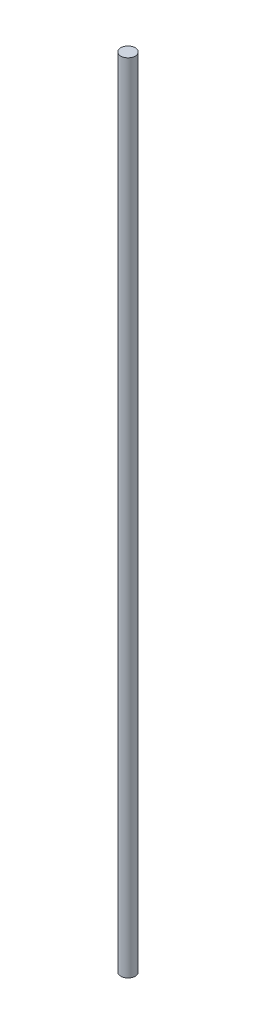
SolidWorks part; units mm, degrees
ref_plane "Front Plane" through (0, 0, 0) normal (0, 0, 1) x (1, 0, 0)
ref_plane "Top Plane" through (0, 0, 0) normal (0, 1, 0) x (1, 0, 0)
ref_plane "Right Plane" through (0, 0, 0) normal (1, 0, 0) x (0, 0, -1)
sketch "Sketch1" plane through (0, 0, 0) normal (0, 1, 0) x (1, 0, 0)
  circle A0 centre (0, 0) radius 4
  dimension "D1" = 8
extrude "Boss-Extrude1" add sketch "Sketch1" along normal up to surface (440 mm away)
